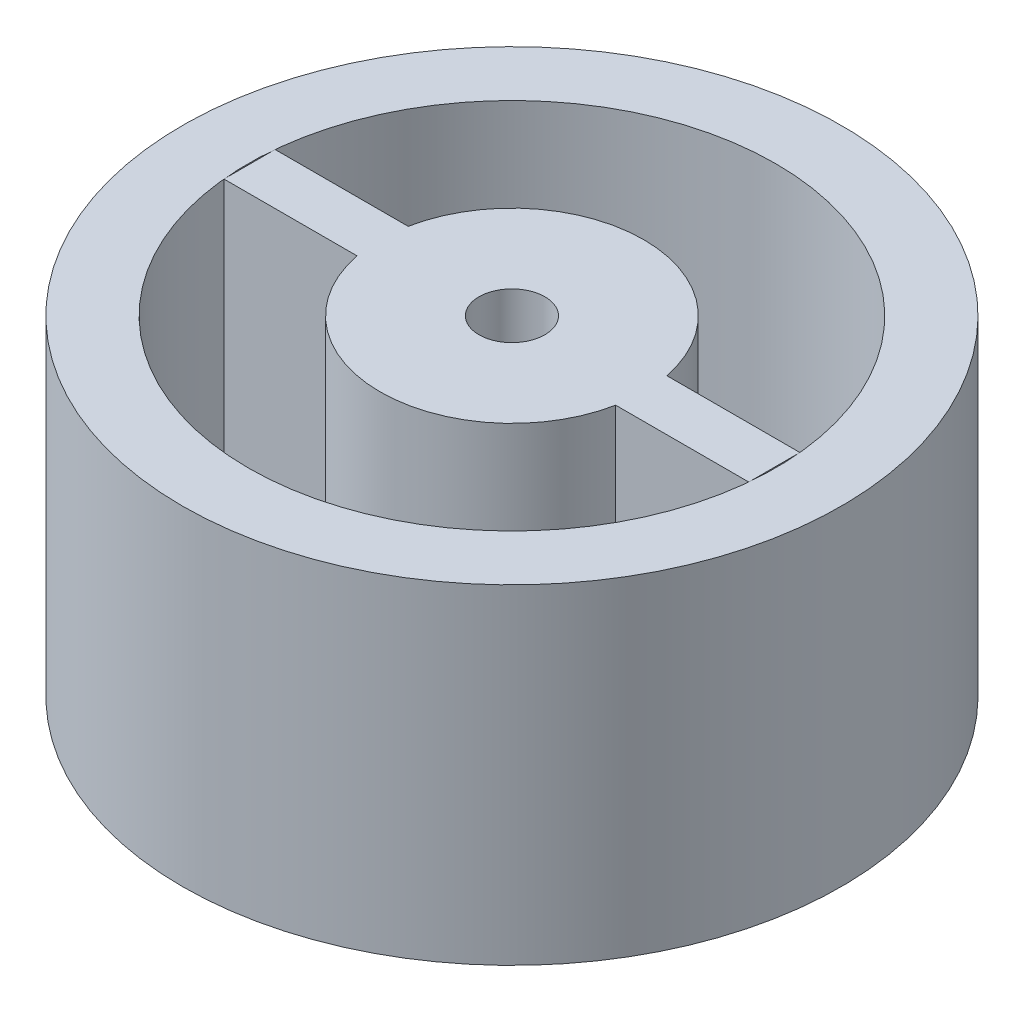
SolidWorks part; units mm, degrees
ref_plane "Front Plane" through (0, 0, 0) normal (0, 0, 1) x (1, 0, 0)
ref_plane "Top Plane" through (0, 0, 0) normal (0, 1, 0) x (1, 0, 0)
ref_plane "Right Plane" through (0, 0, 0) normal (1, 0, 0) x (0, 0, -1)
sketch "Sketch2" plane through (0, 0, 0) normal (0, 1, 0) x (1, 0, 0)
  circle A0 centre (0, 0) radius 5
  circle A1 centre (0, 0) radius 0.5
  dimension "D1" = 10
  dimension "D2" = 1
extrude "Boss-Extrude1" add sketch "Sketch2" along normal blind 5
sketch "Sketch4" plane through (0, 0, 0) normal (0, -1, 0) x (1, 0, 0)
  circle A0 centre (0, 0) radius 4
  circle A1 centre (0, 0) radius 2
  dimension "D1" = 8
  dimension "D2" = 4
extrude "Cut-Extrude1" cut sketch "Sketch4" against normal through all both and the other way through all
sketch "Sketch5" plane through (0, 0, 0) normal (0, -1, 0) x (1, 0, 0)
  line L1 (-3.9812, -0.3878) -> (3.9812, -0.3878)
  line L2 (-3.9812, -0.3878) -> (-3.9812, 0.3878)
  line L3 (-3.9812, 0.3878) -> (3.9812, 0.3878)
  line L4 (3.9812, -0.3878) -> (3.9812, 0.3878)
  line L5 (-3.9812, -0.3878) -> (3.9812, 0.3878) construction
  line L6 (-3.9812, 0.3878) -> (3.9812, -0.3878) construction
  circle A0 centre (0, 0) radius 4 construction
  point P0 (0, 0)
extrude "Boss-Extrude2" add sketch "Sketch5" against normal blind 5
sketch "Sketch6" plane through (0, 0, 0) normal (0, -1, 0) x (1, 0, 0)
  circle A0 centre (0, 0) radius 0.5
extrude "Cut-Extrude2" cut sketch "Sketch6" against normal through all both and the other way through all
